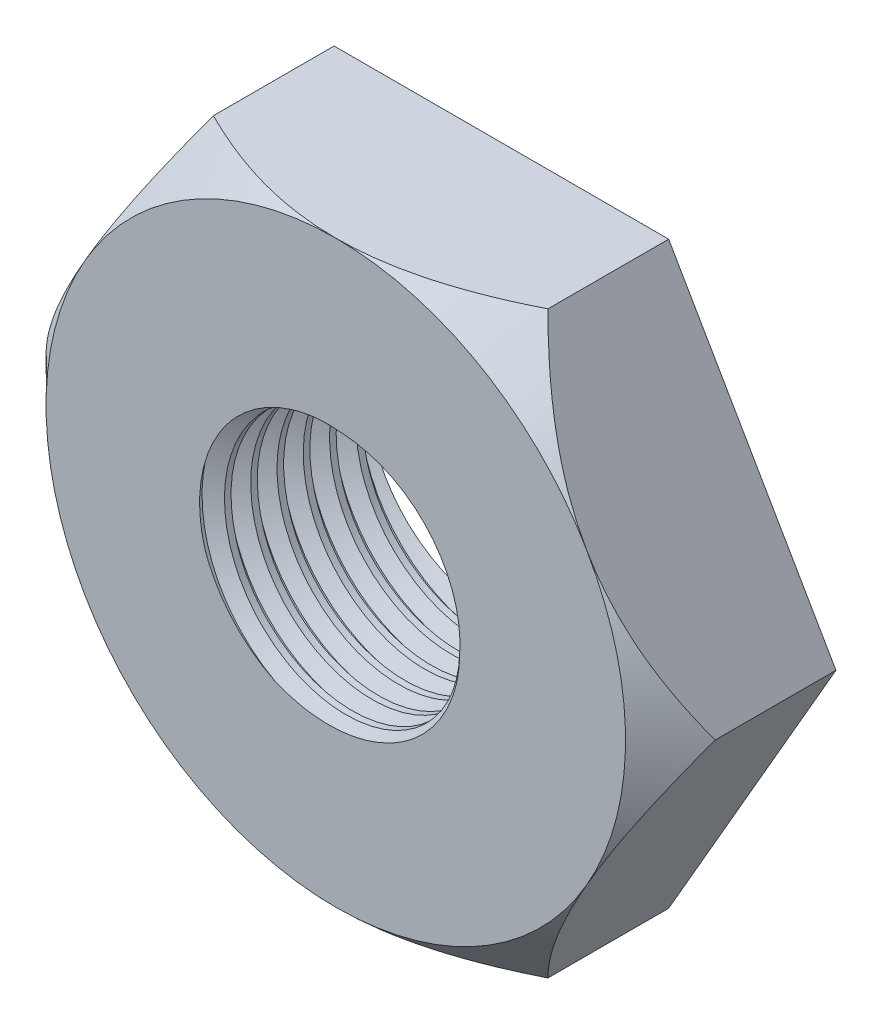
SolidWorks part; units mm, degrees
ref_plane "Front Plane" through (0, 0, 0) normal (0, 0, 1) x (1, 0, 0)
ref_plane "Top Plane" through (0, 0, 0) normal (0, 1, 0) x (1, 0, 0)
ref_plane "Right Plane" through (0, 0, 0) normal (1, 0, 0) x (0, 0, -1)
sketch "Sketch2" plane through (0, 0, 0) normal (0, 0, 1) x (1, 0, 0)
  line L1 (20.2073, 0) -> (10.1036, 17.5)
  line L2 (10.1036, 17.5) -> (-10.1036, 17.5)
  line L3 (-10.1036, 17.5) -> (-20.2073, 0)
  line L4 (-20.2073, 0) -> (-10.1036, -17.5)
  line L5 (-10.1036, -17.5) -> (10.1036, -17.5)
  line L6 (10.1036, -17.5) -> (20.2073, 0)
  circle A0 centre (0, 0) radius 17.5 construction
  dimension "D1" = 35
extrude "Boss-Extrude1" add sketch "Sketch2" along normal mid plane 10
sketch "Sketch3" plane through (0, 0, 0) normal (0, 0, 1) x (1, 0, 0)
  line L0 (-10.1036, 17.5) -> (-20.2073, 0) construction
  circle A0 centre (0, 0) radius 17.5
extrude "Cut-Extrude3" cut sketch "Sketch3" against normal through all draft 45 from offset 5 flip side to cut
sketch "Sketch4" plane through (0, 0, 0) normal (0, 0, 1) x (1, 0, 0)
  circle A0 centre (0, 0) radius 7.5
  dimension "D1" = 15
extrude "Cut-Extrude6" cut sketch "Sketch4" against normal mid plane 50
thread "Thread9" pitch 1.5875 method cut profile "Thread Profile11" start angle 0, offset 2, length 0, pitch 1.5875, diameter 15
ref_plane "Plane11" through (-7.5, 0, 7) normal (0, -1, 0) x (-1, 0, 0)
sketch "Thread Profile11" plane through (-7.5, 0, 7) normal (0, -1, 0) x (-1, 0, 0)
  line L0 (0, 0) -> (0, 1.5875) construction
  line L1 (0, 0) -> (0.8593, 0.4961)
  line L2 (0.8593, 0.4961) -> (0.8593, 0.6945)
  line L3 (0.8593, 0.6945) -> (0, 1.1906)
  line L4 (0.8593, 0.5953) -> (0, 0.5953) construction
  line L11 (0, 0) -> (0, 1.1906)
  point P2 (0, 0)
  dimension "Pitch" = 1.5875
  dimension "Profile_Angle" = 60
  dimension "Profile_Land" = 0.1984
  dimension "Profile_Height" = 0.8593
